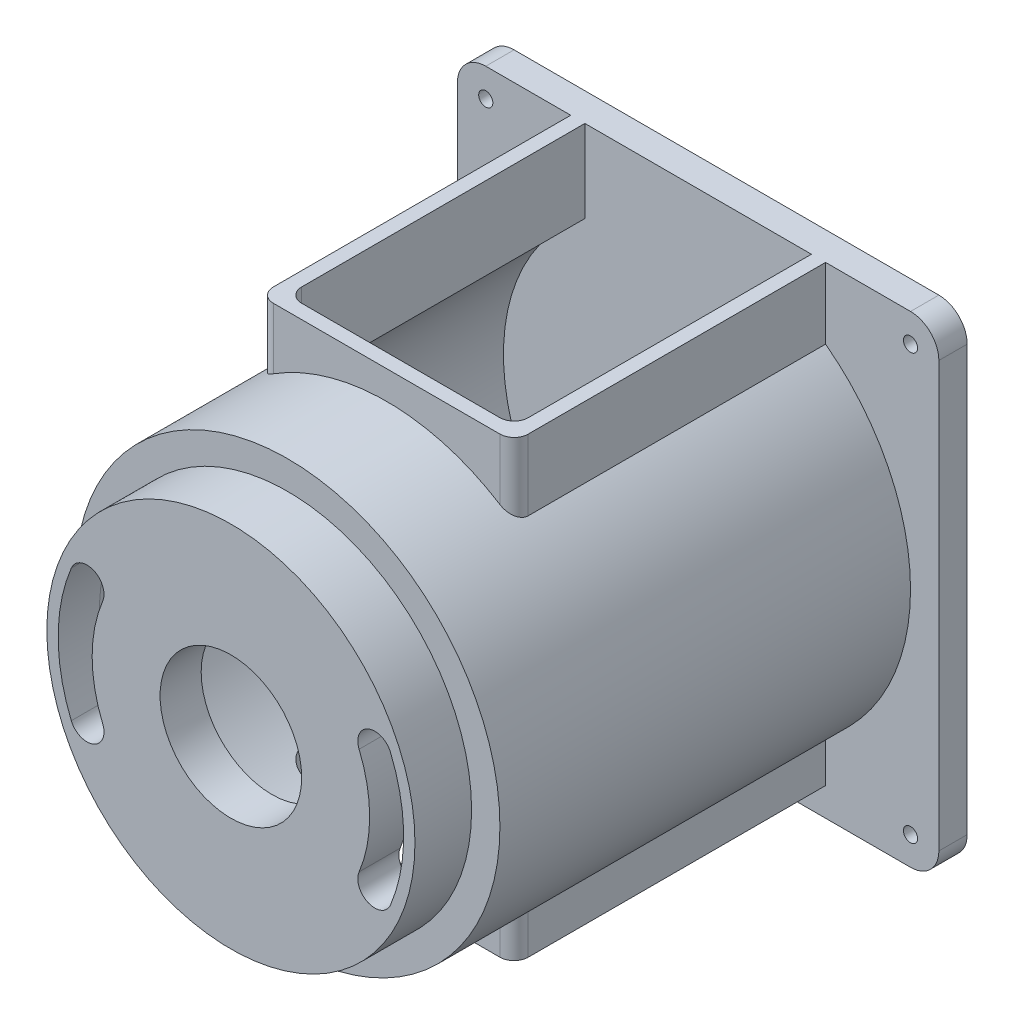
SolidWorks part; units mm, degrees
material "Cast Stainless Steel"
ref_plane "Front Plane" through (0, 0, 0) normal (0, 0, 1) x (1, 0, 0)
ref_plane "Top Plane" through (0, 0, 0) normal (0, 1, 0) x (1, 0, 0)
ref_plane "Right Plane" through (0, 0, 0) normal (1, 0, 0) x (0, 0, -1)
other "Center of Mass"
sketch "Sketch1" plane through (0, 0, 0) normal (0, 1, 0) x (1, 0, 0)
  line L1 (150, -170) -> (-150, -170)
  line L2 (170, -150) -> (170, 150)
  line L3 (150, 170) -> (-150, 170)
  line L4 (-170, -150) -> (-170, 150)
  line L5 (170, -170) -> (-170, 170) construction
  line L6 (170, 170) -> (-170, -170) construction
  arc A0 (170, -150) -> (150, -170) centre (150, -150) cw
  arc A1 (-170, -150) -> (-150, -170) centre (-150, -150) ccw
  arc A2 (150, 170) -> (170, 150) centre (150, 150) cw
  arc A3 (-150, 170) -> (-170, 150) centre (-150, 150) ccw
  point P0 (0, 0)
  dimension "D3" = 20
  dimension "D1" = 340
  dimension "D2" = 340
extrude "Boss-Extrude1" add sketch "Sketch1" along normal blind 20
sketch "Sketch2" plane through (0, 20, 0) normal (0, 1, 0) x (1, 0, 0)
  line L4 (170, -150) -> (170, 150)
  line L5 (150, 170) -> (-150, 170)
  line L6 (-170, 150) -> (-170, -150)
  line L7 (-150, -170) -> (150, -170)
  line L8 (170, -150) -> (170, 150)
  line L9 (150, 170) -> (-150, 170)
  line L10 (-170, 150) -> (-170, -150)
  line L11 (-150, -170) -> (150, -170)
  line L12 (-150, 0) -> (-150, -90)
  line L13 (-150, -90) -> (-120, -90)
  line L14 (120, -90) -> (150, -90)
  line L15 (0, 0) -> (-150, 0) construction
  line L16 (150, -150) -> (150, 150)
  line L17 (150, 150) -> (-150, 150)
  line L18 (-150, 150) -> (-150, -150)
  line L19 (-150, -150) -> (150, -150)
  line L20 (150, -150) -> (150, 150)
  line L21 (150, 150) -> (-150, 150)
  line L22 (-150, 150) -> (-150, -150)
  line L23 (-150, -150) -> (150, -150)
  line L24 (150, -90) -> (170, -90)
  line L25 (150, 90) -> (170, 90)
  line L26 (120, 90) -> (150, 90)
  line L27 (-150, 90) -> (-120, 90)
  arc A4 (150, -170) -> (170, -150) centre (150, -150) ccw
  arc A5 (170, 150) -> (150, 170) centre (150, 150) ccw
  arc A6 (-150, 170) -> (-170, 150) centre (-150, 150) ccw
  arc A7 (-170, -150) -> (-150, -170) centre (-150, -150) ccw
  arc A8 (150, -170) -> (170, -150) centre (150, -150) ccw
  arc A9 (170, 150) -> (150, 170) centre (150, 150) ccw
  arc A10 (-150, 170) -> (-170, 150) centre (-150, 150) ccw
  arc A11 (-170, -150) -> (-150, -170) centre (-150, -150) ccw
  circle A12 centre (0, 0) radius 150
  dimension "D3" = 30
  dimension "D1" = 0
  dimension "D2" = 20
extrude "Boss-Extrude2" add sketch "Sketch2" along normal blind 220 contours A12 | A12 L12 L13 | A12 L14 L20 | L25 L20 L24 L8 | A12 L20 L26 | A12 L27 L22 region at (160, 20, 0) region at (141.1785, 20, 67.9748) region at (141.1785, 20, -67.9748) region at (0, 20, 0) region at (-141.1785, 20, 67.9748) region at (-141.1785, 20, -67.9748)
sketch "Sketch3" plane through (0, 240, 0) normal (0, 1, 0) x (1, 0, 0)
  line L6 (170, -90) -> (170, 90)
  line L7 (170, 90) -> (120, 90)
  line L8 (-120, 90) -> (-150, 90)
  line L9 (-150, 90) -> (-150, -90)
  line L10 (-150, -90) -> (-120, -90)
  line L11 (120, -90) -> (170, -90)
  line L12 (170, -90) -> (170, 90)
  line L13 (170, 90) -> (120, 90)
  line L14 (-120, 90) -> (-150, 90)
  line L15 (-150, 90) -> (-150, -90)
  line L16 (-150, -90) -> (-120, -90)
  line L17 (120, -90) -> (170, -90)
  circle A0 centre (0, 0) radius 150
  arc A2 (120, 90) -> (-120, 90) centre (0, 0) ccw
  arc A3 (-120, -90) -> (120, -90) centre (0, 0) ccw
  arc A4 (120, 90) -> (-120, 90) centre (0, 0) ccw
  arc A5 (-120, -90) -> (120, -90) centre (0, 0) ccw
  arc M11 (120, 90) -> (-120, 90) centre (0, 0) ccw
  arc M15 (-120, -90) -> (120, -90) centre (0, 0) ccw
  dimension "D1" = 0
extrude "Boss-Extrude3" add sketch "Sketch3" along normal blind 70 contours A0 M15 M11 region at (0, 240, 0)
sketch "Sketch4" plane through (0, 310, 0) normal (0, 1, 0) x (1, 0, 0)
  circle A1 centre (0, 0) radius 150
  circle A2 centre (0, 0) radius 150
  circle A4 centre (0, 0) radius 130
  circle A5 centre (0, 0) radius 130
  dimension "D1" = 0
  dimension "D2" = 20
extrude "Boss-Extrude4" add sketch "Sketch4" along normal blind 40 contours A5 region at (0, 310, 0)
fillet "Fillet1" radius 10 4 edges at (-135, 240, 90) (-135, 240, -90) (145, 240, -90) (145, 240, 90)
sketch "Sketch10" plane through (170, 0, 0) normal (1, 0, 0) x (0, 0, -1)
  line L0 (80, 20) -> (80, 220)
  line L1 (70, 230) -> (-70, 230)
  line L2 (-80, 220) -> (-80, 20)
  line L3 (80, 20) -> (80, 230) construction
  line L4 (80, 230) -> (-80, 230) construction
  line L5 (-80, 230) -> (-80, 20) construction
  line L6 (80, 20) -> (-80, 20)
  line L8 (90, 20) -> (90, 230)
  line L9 (80, 240) -> (-80, 240)
  line L10 (-90, 230) -> (-90, 20)
  line L11 (-90, 20) -> (-150, 20)
  line L12 (-150, 20) -> (-150, 0)
  line L13 (-150, 0) -> (150, 0)
  line L14 (150, 0) -> (150, 20)
  line L15 (150, 20) -> (90, 20)
  line L16 (90, 20) -> (90, 230)
  line L17 (80, 240) -> (-80, 240)
  line L18 (-90, 230) -> (-90, 20)
  line L19 (-90, 20) -> (-150, 20)
  line L20 (-150, 20) -> (-150, 0)
  line L21 (-150, 0) -> (150, 0)
  line L22 (150, 0) -> (150, 20)
  line L23 (150, 20) -> (90, 20)
  arc A0 (-80, 220) -> (-70, 230) centre (-70, 220) cw
  arc A2 (90, 230) -> (80, 240) centre (80, 230) ccw
  arc A3 (-80, 240) -> (-90, 230) centre (-80, 230) ccw
  arc A4 (90, 230) -> (80, 240) centre (80, 230) ccw
  arc A5 (-80, 240) -> (-90, 230) centre (-80, 230) ccw
  arc A6 (80, 220) -> (70, 230) centre (70, 220) ccw
  arc A7 (80, 230) -> (80, 230) centre (80, 230) ccw construction
  arc A8 (-80, 230) -> (-80, 230) centre (-80, 230) ccw construction
  dimension "D3" = 10
  dimension "D1" = 0
  dimension "D2" = 10
extrude "Cut-Extrude1" cut sketch "Sketch10" against normal up to surface (320 mm away) contours L0 A6 L1 A0 L2 L6 region at (170, 124.8686, 0) up to face at (-150, 174.8774, 0)
sketch "Sketch14" plane through (0, 20, 0) normal (0, 1, 0) x (1, 0, 0)
  line L0 (170, -80) -> (165, -80)
  line L1 (165, -80) -> (165, 80)
  line L14 (170, -90) -> (120, -90)
  line L15 (-120, -90) -> (-150, -90)
  line L16 (-150, -90) -> (-150, -80)
  line L17 (-150, -80) -> (170, -80)
  line L18 (170, -80) -> (170, 80)
  line L19 (170, 80) -> (-150, 80)
  line L20 (-150, 80) -> (-150, 90)
  line L21 (-150, 90) -> (-120, 90)
  line L22 (120, 90) -> (170, 90)
  line L23 (170, 90) -> (170, 150)
  line L24 (150, 170) -> (-150, 170)
  line L25 (-170, 150) -> (-170, -150)
  line L26 (-150, -170) -> (150, -170)
  line L27 (170, -150) -> (170, -90)
  line L28 (170, -90) -> (120, -90)
  line L29 (-120, -90) -> (-150, -90)
  line L30 (-150, -90) -> (-150, -80)
  line L31 (-150, -80) -> (170, -80)
  line L32 (170, -80) -> (170, 80)
  line L33 (170, 80) -> (-150, 80)
  line L34 (-150, 80) -> (-150, 90)
  line L35 (-150, 90) -> (-120, 90)
  line L36 (120, 90) -> (170, 90)
  line L37 (170, 90) -> (170, 150)
  line L38 (150, 170) -> (-150, 170)
  line L39 (-170, 150) -> (-170, -150)
  line L40 (-150, -170) -> (150, -170)
  line L41 (170, -150) -> (170, -90)
  arc A6 (-120, -90) -> (120, -90) centre (0, 0) ccw
  arc A7 (120, 90) -> (-120, 90) centre (0, 0) ccw
  arc A8 (170, 150) -> (150, 170) centre (150, 150) ccw
  arc A9 (-150, 170) -> (-170, 150) centre (-150, 150) ccw
  arc A10 (-170, -150) -> (-150, -170) centre (-150, -150) ccw
  arc A11 (150, -170) -> (170, -150) centre (150, -150) ccw
  arc A12 (-120, -90) -> (120, -90) centre (0, 0) ccw
  arc A13 (120, 90) -> (-120, 90) centre (0, 0) ccw
  arc A14 (170, 150) -> (150, 170) centre (150, 150) ccw
  arc A15 (-150, 170) -> (-170, 150) centre (-150, 150) ccw
  arc A16 (-170, -150) -> (-150, -170) centre (-150, -150) ccw
  arc A17 (150, -170) -> (170, -150) centre (150, -150) ccw
  line M26 (-150, -80) -> (170, -80)
  line M27 (170, -80) -> (170, 80)
  line M28 (170, 80) -> (-150, 80)
  dimension "D2" = 5
  dimension "D1" = 0
extrude "Boss-Extrude9" add sketch "Sketch14" along normal up to surface (210 mm away) contours L1 M26 M27 M28 region at (167.5, 20, 0) up to face at (10, 230, 0)
sketch "Sketch15" plane through (170, 0, 0) normal (1, 0, 0) x (0, 0, -1)
  line L0 (0, 0) -> (0, 50)
  line L1 (-150, 0) -> (150, 0) construction
  circle A0 centre (0, 50) radius 15
  dimension "D1" = 50
extrude "Cut-Extrude4" cut sketch "Sketch15" against normal up to surface (5 mm away) contours A0 region at (170, 39.6934, -10.3066) up to face at (165, 157.357, 0)
sketch "Sketch16" plane through (170, 0, 0) normal (1, 0, 0) x (0, 0, -1)
  line L0 (80, 10) -> (80, 220)
  line L1 (70, 230) -> (-70, 230)
  line L2 (-80, 220) -> (-80, 10)
  line L3 (-80, 10) -> (-140, 10)
  line L4 (-140, 10) -> (-140, 10)
  line L5 (-140, 10) -> (140, 10)
  line L6 (140, 10) -> (140, 10)
  line L7 (140, 10) -> (80, 10)
  line L8 (90, 20) -> (90, 230)
  line L9 (80, 240) -> (-80, 240)
  line L10 (-90, 230) -> (-90, 20)
  line L11 (-90, 20) -> (-150, 20)
  line L12 (-150, 20) -> (-150, 0)
  line L13 (-150, 0) -> (150, 0)
  line L14 (150, 0) -> (150, 20)
  line L15 (150, 20) -> (90, 20)
  line L16 (90, 20) -> (90, 230)
  line L17 (80, 240) -> (-80, 240)
  line L18 (-90, 230) -> (-90, 20)
  line L19 (-90, 20) -> (-150, 20)
  line L20 (-150, 20) -> (-150, 0)
  line L21 (-150, 0) -> (150, 0)
  line L22 (150, 0) -> (150, 20)
  line L23 (150, 20) -> (90, 20)
  line L24 (80, 10) -> (80, 230) construction
  line L25 (80, 230) -> (-80, 230) construction
  line L26 (-80, 230) -> (-80, 10) construction
  line L27 (-90, 20) -> (90, 20)
  arc A0 (-80, 220) -> (-70, 230) centre (-70, 220) cw
  arc A2 (90, 230) -> (80, 240) centre (80, 230) ccw
  arc A3 (-80, 240) -> (-90, 230) centre (-80, 230) ccw
  arc A4 (90, 230) -> (80, 240) centre (80, 230) ccw
  arc A5 (-80, 240) -> (-90, 230) centre (-80, 230) ccw
  arc A6 (80, 220) -> (70, 230) centre (70, 220) ccw
  arc A7 (80, 230) -> (80, 230) centre (80, 230) ccw construction
  arc A8 (-80, 230) -> (-80, 230) centre (-80, 230) ccw construction
  circle M11 centre (0, 50) radius 15
  dimension "D3" = 10
  dimension "D1" = 0
  dimension "D2" = 10
extrude "Cut-Extrude5" cut sketch "Sketch16" against normal blind 10 contours L0 A6 L1 A0 L2 L27 M11 region at (170, 126.4796, 0)
sketch "Sketch18" plane through (0, 20, 0) normal (0, 1, 0) x (1, 0, 0)
  circle A0 centre (0, 0) radius 137.5
  dimension "D1" = 275
extrude "Cut-Extrude6" cut sketch "Sketch18" along normal blind 256
ref_point "Point1"
move or copy body "Body-Move/Copy1" bodies to move or copy 115 copy no rotation origin (0, 0, 0) rotation axis (1, 0, 0) rotation angle 90
move or copy body "Body-Move/Copy2" bodies to move or copy 118 copy no rotation origin (0, 0, 0) rotation axis (0, 0, -1) rotation angle 90
move or copy body "Body-Move/Copy3" bodies to move or copy 119 copy no rotation origin (0, 0, 0) rotation axis (0, 0, 1) rotation angle 180
sketch "Sketch19" plane through (0, 0, 350) normal (0, 0, 1) x (1, 0, 0)
  circle A0 centre (0, 0) radius 50
  dimension "D1" = 100
extrude "Cut-Extrude7" cut sketch "Sketch19" against normal up to surface (74 mm away) up to face at (137.5, 0, 276)
sketch "Sketch20" plane through (0, 0, 0) normal (0, 0, -1) x (-1, 0, 0)
  line L1 (-150, 150) -> (150, 150)
  line L2 (-150, 150) -> (-150, -150)
  line L3 (-150, -150) -> (150, -150)
  line L4 (150, 150) -> (150, -150)
  line L5 (-150, 150) -> (150, -150) construction
  line L6 (-150, -150) -> (150, 150) construction
  circle A0 centre (150, -150) radius 5
  circle A1 centre (-150, -150) radius 5
  circle A2 centre (-150, 150) radius 5
  circle A3 centre (150, 150) radius 5
  point P0 (0, 0)
  point P7 (150, -150)
  point P8 (-150, -150)
  point P9 (150, 150)
  point P10 (-150, 150)
  dimension "D3" = 10
  dimension "D4" = 10
  dimension "D5" = 10
  dimension "D6" = 10
  dimension "D1" = 300
  dimension "D2" = 300
extrude "Cut-Extrude8" cut sketch "Sketch20" against normal up to surface (20 mm away) contours L3 A0 L4 | L4 A0 L3 | L2 A1 L3 | L3 A1 L2 | L1 A2 L2 | L2 A2 L1 | L4 A3 L1 | L1 A3 L4 region at (150.7074, 150.7074, 0) region at (147.8779, 147.8779, 0) region at (-150.7074, 150.7074, 0) region at (-147.8779, 147.8779, 0) region at (147.8779, -147.8779, 0) region at (150.7074, -150.7074, 0) region at (-150.7074, -150.7074, 0) region at (-147.8779, -147.8779, 0) up to face at (0, 170, 157.357)
sketch "Sketch26" plane through (0, 0, 350) normal (0, 0, 1) x (1, 0, 0)
  line L0 (0, 0) -> (0, 110) construction
  line L1 (0, 0) -> (42.0952, 101.6267) construction
  line L2 (0, 0) -> (101.6267, -42.0952) construction
  line L3 (0, 0) -> (110, 0) construction
  line L4 (0, 0) -> (101.6267, 42.0952) construction
  circle A0 centre (0, 0) radius 110
  circle A1 centre (0, 0) radius 130
  circle A2 centre (0, 0) radius 130
  circle A3 centre (101.6267, -42.0952) radius 12
  circle A4 centre (110, 0) radius 12
  circle A5 centre (0, 0) radius 98
  circle A6 centre (0, 0) radius 122
  circle A7 centre (101.6267, 42.0952) radius 12
  point P14 (0, 0)
  dimension "D2" = 220
  dimension "D4" = 24
  dimension "D5" = 24
  dimension "D8" = 196
  dimension "D9" = 244
  dimension "D10" = 24
  dimension "D3" = 22.5
  dimension "D6" = 22.5
  dimension "D7" = 22.5
  dimension "D1" = 0
extrude "Cut-Extrude11" cut sketch "Sketch26" against normal up to surface (74 mm away) contours A0 A3 | A0 A3 | A3 A6 A4 A0 | A5 A3 A0 A4 | A0 A4 | A7 A5 A4 A0 | A7 A0 A4 A6 | A7 A0 | A0 A7 | A0 A4 region at (104.791, 0, 350) region at (114.9732, 0, 350) region at (101.2141, 20.1327, 350) region at (114.2829, 22.7323, 350) region at (114.2829, -22.7323, 350) region at (101.2141, -20.1327, 350) region at (96.8142, 40.1018, 350) region at (106.2214, 43.9984, 350) region at (106.2214, -43.9984, 350) region at (96.8142, -40.1018, 350) up to face at (50, 0, 276)
sketch "Sketch29" plane through (0, 0, 276) normal (0, 0, -1) x (-1, 0, 0)
  circle A0 centre (0, 0) radius 122.5
  circle A1 centre (0, 0) radius 137.5
  circle A2 centre (0, 0) radius 137.5
  arc M2 (-90.5402, -37.503) -> (-112.7133, -46.6874) centre (-101.6267, -42.0952) cw
  arc M3 (-112.7133, -46.6874) -> (-112.7133, 46.6874) centre (0, 0) cw
  arc M4 (-112.7133, 46.6874) -> (-90.5402, 37.503) centre (-101.6267, 42.0952) cw
  arc M5 (-90.5402, 37.503) -> (-90.5402, -37.503) centre (0, 0) ccw
  circle M6 centre (0, 0) radius 50
  dimension "D1" = 0
  dimension "D2" = 15
extrude "Cut-Extrude12" cut sketch "Sketch29" against normal blind 45 contours A0 M5 M2 M3 M4 M6 region at (122.1535, 0, 276)
mirror "Mirror1" about plane through (0, 0, 0) normal (1, 0, 0) of "Cut-Extrude11"
